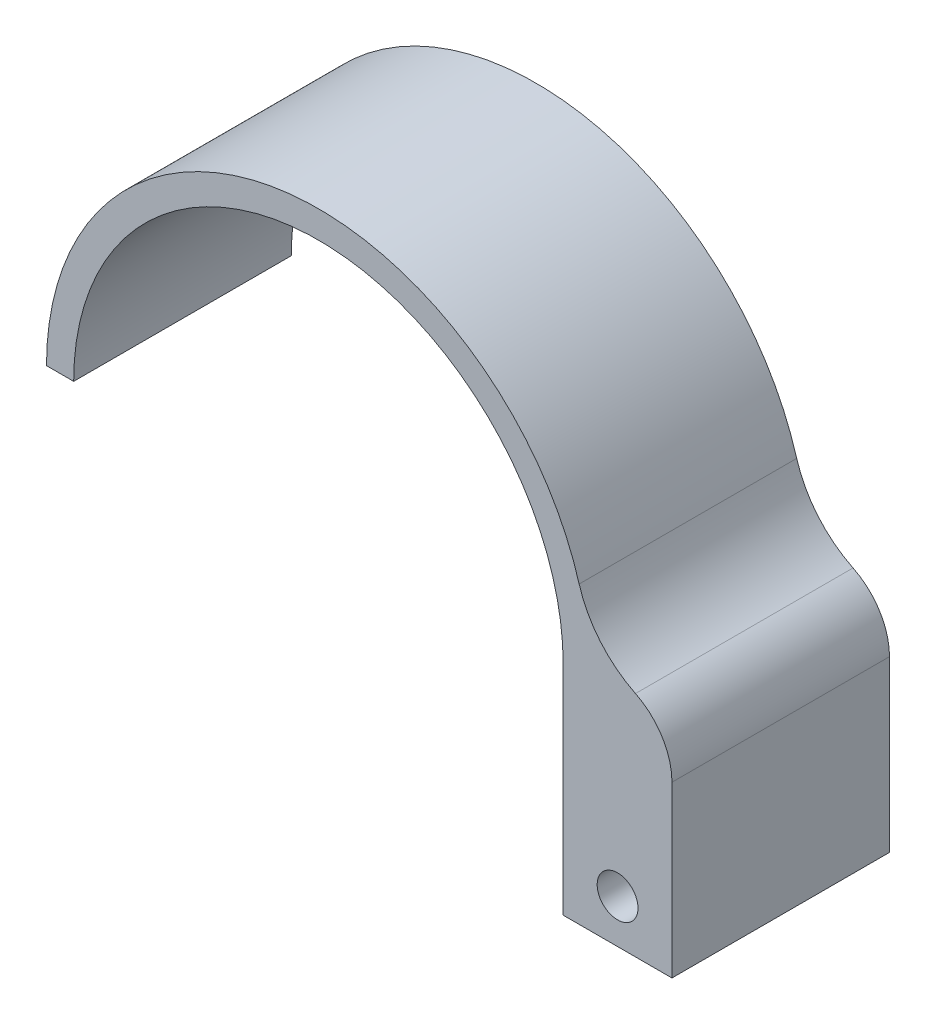
SolidWorks part; units mm, degrees
material "ABS"
ref_plane "Front Plane" through (0, 0, 0) normal (0, 0, 1) x (1, 0, 0)
ref_plane "Top Plane" through (0, 0, 0) normal (0, 1, 0) x (1, 0, 0)
ref_plane "Right Plane" through (0, 0, 0) normal (1, 0, 0) x (0, 0, -1)
sketch "Sketch1" plane through (0, 0, 0) normal (0, 0, 1) x (1, 0, 0)
  line L0 (-31.75, 0) -> (31.75, 0)
  line L2 (28.575, 0) -> (41.275, 0)
  line L3 (28.575, 0) -> (28.575, -25.4)
  line L4 (28.575, -25.4) -> (41.275, -25.4)
  line L5 (41.275, 0) -> (41.275, -25.4)
  circle A0 centre (0, 0) radius 31.75
  circle A1 centre (0, 0) radius 28.575
  dimension "D1" = 63.5
  dimension "D2" = 57.15
  dimension "D3" = 12.7
  dimension "D4" = 25.4
extrude "Boss-Extrude1" add sketch "Sketch1" along normal blind 25.4 contours A1 L0 A0 | A0 L3 L4 L5 L2 | L3 A0 L0 region at (0, 29.285, 0) region at (29.8506, -5.2263, 0) region at (35.4377, -13.4551, 0)
fillet "Fillet1" radius 12.7 1 edges at (31.75, 0, 12.7)
fillet "Fillet2" radius 7.62 1 edges at (41.275, 0, 12.7)
sketch "Sketch2" plane through (0, -25.4, 0) normal (0, -1, 0) x (-1, 0, 0)
  line L0 (-41.275, -25.4) -> (-41.275, 0) construction
  line L1 (-38.4748, -15.875) -> (-31.3752, -15.875)
  line L2 (-38.4748, -9.525) -> (-31.3752, -9.525)
  line L3 (-28.575, -25.4) -> (-41.275, -25.4) construction
  circle A0 centre (-34.925, -12.7) radius 4.7625
  point P8 (-37.1822, -14.0872)
  point P9 (-34.925, -14.4813)
  point P10 (-30.0355, -11.0583)
  point P11 (-39.3799, -12.6348)
  dimension "D1" = 9.525
  dimension "D2" = 6.35
  dimension "D3" = 6.35
  dimension "D4" = 3.175
  dimension "D5" = 12.7
extrude "Cut-Extrude1" cut sketch "Sketch2" against normal blind 21.59 contours L2 A0 L1 region at (34.925, -25.4, 12.7)
sketch "Sketch3" plane through (0, -25.4, 0) normal (0, -1, 0) x (1, 0, 0)
  circle A0 centre (34.925, 12.7) radius 4.7625
  arc A1 (38.4748, 9.525) -> (38.4748, 15.875) centre (34.925, 12.7) ccw construction
extrude "Cut-Extrude2" cut sketch "Sketch3" against normal blind 2.54
sketch "Sketch4" plane through (0, 0, 25.4) normal (0, 0, 1) x (1, 0, 0)
  line L0 (28.575, -25.4) -> (41.275, -25.4) construction
  line L1 (41.275, -5.6075) -> (41.275, -25.4) construction
  circle A0 centre (34.925, -20.32) radius 2.3812
  dimension "D1" = 4.7625
  dimension "D2" = 5.08
  dimension "D3" = 6.35
extrude "Cut-Extrude3" cut sketch "Sketch4" against normal through all
